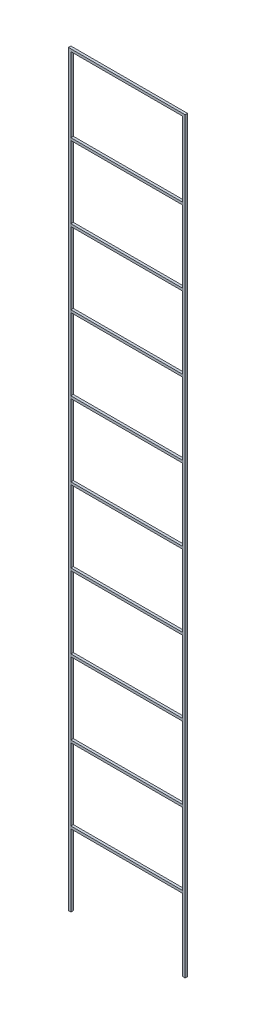
SolidWorks part; units mm, degrees
ref_plane "Front Plane" through (0, 0, 0) normal (0, 0, 1) x (1, 0, 0)
ref_plane "Top Plane" through (0, 0, 0) normal (0, 1, 0) x (1, 0, 0)
ref_plane "Right Plane" through (0, 0, 0) normal (1, 0, 0) x (0, 0, -1)
sketch "Sketch2" plane through (0, 0, 0) normal (0, 0, 1) x (1, 0, 0)
  line L0 (0, -92.3755) -> (0, -3140.3755)
  line L1 (-457.2, -92.3755) -> (-457.2, -3140.3755)
  line L2 (-457.2, -397.1755) -> (0, -397.1755)
  line L3 (-457.2, -1616.3755) -> (0, -1616.3755)
  line L4 (-457.2, -2530.7755) -> (0, -2530.7755)
  line L5 (-457.2, -701.9755) -> (0, -701.9755)
  line L6 (-457.2, -2225.9755) -> (0, -2225.9755)
  line L7 (-457.2, -1006.7755) -> (0, -1006.7755)
  line L8 (-457.2, -1311.5755) -> (0, -1311.5755)
  line L9 (-457.2, -1921.1755) -> (0, -1921.1755)
  line L10 (-457.2, -92.3755) -> (0, -92.3755)
  line L11 (-457.2, -2835.5755) -> (0, -2835.5755)
  point P0 (0, -3140.3755)
  point P15 (285.3754, -2589.9215)
  point P26 (-228.6, -1616.3755)
  dimension "D1" = 3048
  dimension "D2" = 457.2
  dimension "D3" = 304.8
  dimension "D4" = 304.8
  dimension "D5" = 304.8
  dimension "D6" = 304.8
  dimension "D7" = 304.8
  dimension "D8" = 304.8
  dimension "D9" = 304.8
  dimension "D10" = 304.8
  dimension "D11" = 3048
extrude "Extrude-Thin1" add sketch "Sketch2" along normal blind 10 thin thin type one direction wall 10
